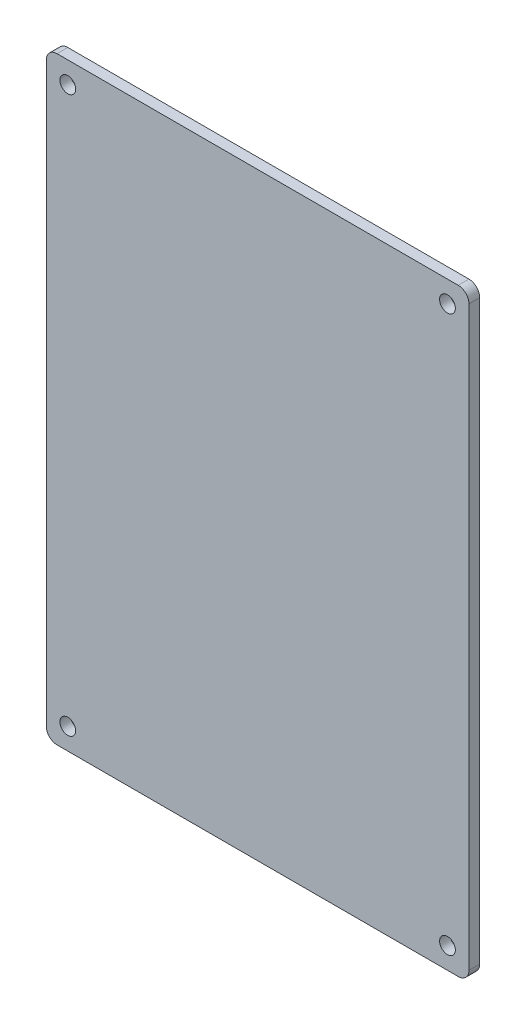
SolidWorks part; units mm, degrees
ref_plane "Plan de face" through (0, 0, 0) normal (0, 0, 1) x (1, 0, 0)
ref_plane "Plan de dessus" through (0, 0, 0) normal (0, 1, 0) x (1, 0, 0)
ref_plane "Plan de droite" through (0, 0, 0) normal (1, 0, 0) x (0, 0, -1)
sketch "Esquisse3" plane through (0, 0, 1) normal (0, 0, 1) x (1, 0, 0)
  line L4 (-14.3355, 46.8744) -> (-14.3355, -33.7056)
  line L5 (-12.8355, -35.2056) -> (43.1745, -35.2056)
  line L6 (44.6745, -33.7056) -> (44.6745, 46.8744)
  line L7 (43.1745, 48.3744) -> (-12.8355, 48.3744)
  line L8 (-14.3355, 46.8744) -> (-14.3355, -33.7056)
  line L9 (-12.8355, -35.2056) -> (43.1745, -35.2056)
  line L10 (44.6745, -33.7056) -> (44.6745, 46.8744)
  line L11 (43.1745, 48.3744) -> (-12.8355, 48.3744)
  arc A4 (-14.3355, -33.7056) -> (-12.8355, -35.2056) centre (-12.8355, -33.7056) ccw
  arc A5 (43.1745, -35.2056) -> (44.6745, -33.7056) centre (43.1745, -33.7056) ccw
  arc A6 (44.6745, 46.8744) -> (43.1745, 48.3744) centre (43.1745, 46.8744) ccw
  arc A7 (-12.8355, 48.3744) -> (-14.3355, 46.8744) centre (-12.8355, 46.8744) ccw
  arc A8 (-14.3355, -33.7056) -> (-12.8355, -35.2056) centre (-12.8355, -33.7056) ccw
  arc A9 (43.1745, -35.2056) -> (44.6745, -33.7056) centre (43.1745, -33.7056) ccw
  arc A10 (44.6745, 46.8744) -> (43.1745, 48.3744) centre (43.1745, 46.8744) ccw
  arc A11 (-12.8355, 48.3744) -> (-14.3355, 46.8744) centre (-12.8355, 46.8744) ccw
  dimension "D1" = 0
extrude "Lid_Base" add sketch "Esquisse3" along normal blind 1.5
sketch "Esquisse4" plane through (0, 0, 1) normal (0, 0, -1) x (-1, 0, 0)
  line L12 (7.1355, 44.6744) -> (-37.4745, 44.6744)
  line L13 (-37.4745, 44.6744) -> (-37.4745, 43.8744)
  line L14 (-40.1745, 41.1744) -> (-40.9745, 41.1744)
  line L15 (-40.9745, 41.1744) -> (-40.9745, -28.0056)
  line L16 (-40.9745, -28.0056) -> (-40.1745, -28.0056)
  line L17 (-37.4745, -30.7056) -> (-37.4745, -31.5056)
  line L18 (-37.4745, -31.5056) -> (7.1355, -31.5056)
  line L19 (7.1355, -31.5056) -> (7.1355, -30.7056)
  line L20 (9.8355, -28.0056) -> (10.6355, -28.0056)
  line L21 (10.6355, -28.0056) -> (10.6355, 41.1744)
  line L22 (10.6355, 41.1744) -> (9.8355, 41.1744)
  line L23 (7.1355, 43.8744) -> (7.1355, 44.6744)
  line L72 (7.3355, 45.8744) -> (-37.6745, 45.8744)
  line L73 (-38.6745, 44.8744) -> (-38.6745, 43.8744)
  line L74 (-40.1745, 42.3744) -> (-41.1745, 42.3744)
  line L75 (-42.1745, 41.3744) -> (-42.1745, -28.2056)
  line L76 (-41.1745, -29.2056) -> (-40.1745, -29.2056)
  line L77 (-38.6745, -30.7056) -> (-38.6745, -31.7056)
  line L78 (-37.6745, -32.7056) -> (7.3355, -32.7056)
  line L79 (8.3355, -31.7056) -> (8.3355, -30.7056)
  line L80 (9.8355, -29.2056) -> (10.8355, -29.2056)
  line L81 (11.8355, -28.2056) -> (11.8355, 41.3744)
  line L82 (10.8355, 42.3744) -> (9.8355, 42.3744)
  line L83 (8.3355, 43.8744) -> (8.3355, 44.8744)
  line L84 (7.3355, 45.8744) -> (-37.6745, 45.8744)
  line L85 (-38.6745, 44.8744) -> (-38.6745, 43.8744)
  line L86 (-40.1745, 42.3744) -> (-41.1745, 42.3744)
  line L87 (-42.1745, 41.3744) -> (-42.1745, -28.2056)
  line L88 (-41.1745, -29.2056) -> (-40.1745, -29.2056)
  line L89 (-38.6745, -30.7056) -> (-38.6745, -31.7056)
  line L90 (-37.6745, -32.7056) -> (7.3355, -32.7056)
  line L91 (8.3355, -31.7056) -> (8.3355, -30.7056)
  line L92 (9.8355, -29.2056) -> (10.8355, -29.2056)
  line L93 (11.8355, -28.2056) -> (11.8355, 41.3744)
  line L94 (10.8355, 42.3744) -> (9.8355, 42.3744)
  line L95 (8.3355, 43.8744) -> (8.3355, 44.8744)
  arc A12 (-37.4745, 44.6744) -> (-37.4745, 44.6744) centre (-37.4745, 44.6744) ccw
  arc A13 (-40.1745, 41.1744) -> (-37.4745, 43.8744) centre (-40.1745, 43.8744) ccw
  arc A15 (-40.9745, 41.1744) -> (-40.9745, 41.1744) centre (-40.9745, 41.1744) ccw
  arc A17 (-40.9745, -28.0056) -> (-40.9745, -28.0056) centre (-40.9745, -28.0056) ccw
  arc A19 (-37.4745, -30.7056) -> (-40.1745, -28.0056) centre (-40.1745, -30.7056) ccw
  arc A21 (-37.4745, -31.5056) -> (-37.4745, -31.5056) centre (-37.4745, -31.5056) ccw
  arc A22 (7.1355, -31.5056) -> (7.1355, -31.5056) centre (7.1355, -31.5056) ccw
  arc A23 (9.8355, -28.0056) -> (7.1355, -30.7056) centre (9.8355, -30.7056) ccw
  arc A76 (-37.6745, 45.8744) -> (-38.6745, 44.8744) centre (-37.6745, 44.8744) ccw
  arc A77 (-40.1745, 42.3744) -> (-38.6745, 43.8744) centre (-40.1745, 43.8744) ccw
  arc A78 (-41.1745, 42.3744) -> (-42.1745, 41.3744) centre (-41.1745, 41.3744) ccw
  arc A79 (-42.1745, -28.2056) -> (-41.1745, -29.2056) centre (-41.1745, -28.2056) ccw
  arc A80 (-38.6745, -30.7056) -> (-40.1745, -29.2056) centre (-40.1745, -30.7056) ccw
  arc A81 (-38.6745, -31.7056) -> (-37.6745, -32.7056) centre (-37.6745, -31.7056) ccw
  arc A82 (7.3355, -32.7056) -> (8.3355, -31.7056) centre (7.3355, -31.7056) ccw
  arc A83 (9.8355, -29.2056) -> (8.3355, -30.7056) centre (9.8355, -30.7056) ccw
  arc A84 (10.8355, -29.2056) -> (11.8355, -28.2056) centre (10.8355, -28.2056) ccw
  arc A85 (11.8355, 41.3744) -> (10.8355, 42.3744) centre (10.8355, 41.3744) ccw
  arc A86 (8.3355, 43.8744) -> (9.8355, 42.3744) centre (9.8355, 43.8744) ccw
  arc A87 (8.3355, 44.8744) -> (7.3355, 45.8744) centre (7.3355, 44.8744) ccw
  arc A88 (-37.6745, 45.8744) -> (-38.6745, 44.8744) centre (-37.6745, 44.8744) ccw
  arc A89 (-40.1745, 42.3744) -> (-38.6745, 43.8744) centre (-40.1745, 43.8744) ccw
  arc A90 (-41.1745, 42.3744) -> (-42.1745, 41.3744) centre (-41.1745, 41.3744) ccw
  arc A91 (-42.1745, -28.2056) -> (-41.1745, -29.2056) centre (-41.1745, -28.2056) ccw
  arc A92 (-38.6745, -30.7056) -> (-40.1745, -29.2056) centre (-40.1745, -30.7056) ccw
  arc A93 (-38.6745, -31.7056) -> (-37.6745, -32.7056) centre (-37.6745, -31.7056) ccw
  arc A94 (7.3355, -32.7056) -> (8.3355, -31.7056) centre (7.3355, -31.7056) ccw
  arc A95 (9.8355, -29.2056) -> (8.3355, -30.7056) centre (9.8355, -30.7056) ccw
  arc A96 (10.8355, -29.2056) -> (11.8355, -28.2056) centre (10.8355, -28.2056) ccw
  arc A97 (11.8355, 41.3744) -> (10.8355, 42.3744) centre (10.8355, 41.3744) ccw
  arc A98 (8.3355, 43.8744) -> (9.8355, 42.3744) centre (9.8355, 43.8744) ccw
  arc A99 (8.3355, 44.8744) -> (7.3355, 45.8744) centre (7.3355, 44.8744) ccw
  arc A100 (10.6355, -28.0056) -> (10.6355, -28.0056) centre (10.6355, -28.0056) ccw
  arc A101 (10.6355, 41.1744) -> (10.6355, 41.1744) centre (10.6355, 41.1744) ccw
  arc A102 (7.1355, 43.8744) -> (9.8355, 41.1744) centre (9.8355, 43.8744) ccw
  arc A103 (7.1355, 44.6744) -> (7.1355, 44.6744) centre (7.1355, 44.6744) ccw
  dimension "D1" = 0
  dimension "D2" = 1.2
extrude "Insert" add sketch "Esquisse4" along normal blind 2
fillet "Congé1" radius 1 8 edges at (-10.6355, 6.5844, 1) (-7.9263, -28.7964, 1) (15.1695, -31.5056, 1) (38.2653, -28.7964, 1) (40.9745, 6.5844, 1) (38.2653, 41.9652, 1) (15.1695, 44.6744, 1) (-7.9263, 41.9652, 1)
sketch "Esquisse5" plane through (0, 0, 2.5) normal (0, 0, 1) x (1, 0, 0)
  circle A0 centre (-11.3355, -32.2056) radius 1.1 construction
  circle A1 centre (-11.3355, -32.2056) radius 1.1
  circle A2 centre (-11.3355, 45.3744) radius 1.1 construction
  circle A3 centre (41.6745, 45.3744) radius 1.1 construction
  circle A4 centre (41.6745, -32.2056) radius 1.1 construction
  circle A5 centre (-11.3355, 45.3744) radius 1.1
  circle A6 centre (41.6745, 45.3744) radius 1.1
  circle A7 centre (41.6745, -32.2056) radius 1.1
extrude "M3_Hole" cut sketch "Esquisse5" against normal up to next
